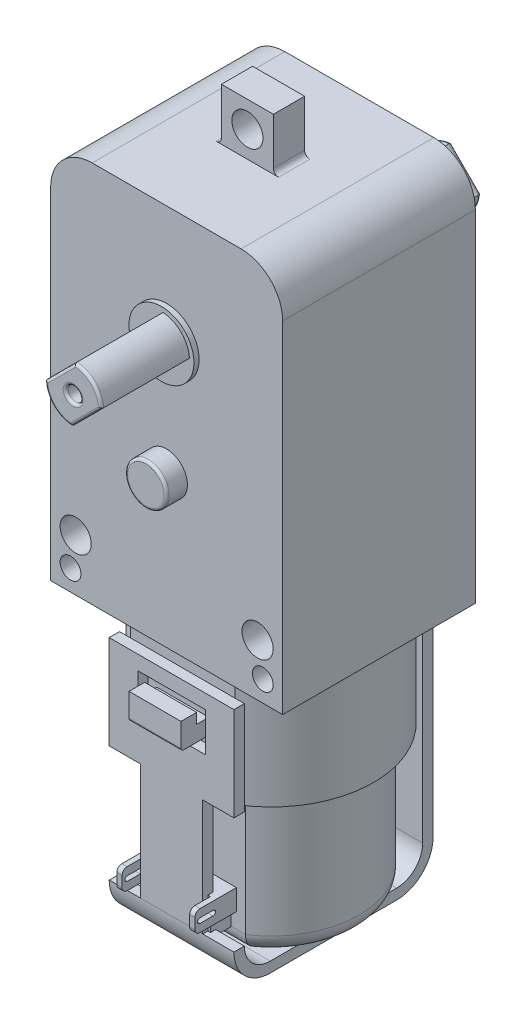
SolidWorks part; units mm, degrees
ref_plane "Front Plane" through (0, 0, 0) normal (0, 0, 1) x (1, 0, 0)
ref_plane "Top Plane" through (0, 0, 0) normal (0, 1, 0) x (1, 0, 0)
ref_plane "Right Plane" through (0, 0, 0) normal (1, 0, 0) x (0, 0, -1)
sketch "Sketch1" plane through (0, 0, 0) normal (0, 0, 1) x (1, 0, 0)
  line L0 (0, 24.4324) -> (0, -59.3504) construction
  line L1 (-11.16, -18.4) -> (11.16, -18.4)
  line L2 (-11.16, -18.4) -> (-11.16, 14.4)
  line L3 (-7.16, 18.4) -> (7.16, 18.4)
  line L4 (11.16, -18.4) -> (11.16, 14.4)
  line L5 (-11.16, -18.4) -> (11.16, 18.4) construction
  line L6 (-11.16, 18.4) -> (11.16, -18.4) construction
  line L7 (8.75, 21.9889) -> (8.75, -24.3513) construction
  line L8 (4.4968, -13.4) -> (12.7809, -13.4) construction
  arc A0 (7.16, 18.4) -> (11.16, 14.4) centre (7.16, 14.4) cw
  arc A1 (-11.16, 14.4) -> (-7.16, 18.4) centre (-7.16, 14.4) cw
  circle A2 centre (8.75, -13.4) radius 1.5
  circle A4 centre (-8.75, -13.4) radius 1.5
  point P0 (0, 0)
  dimension "D3" = 4
  dimension "D7" = 3
  dimension "D1" = 22.32
  dimension "D2" = 36.8
  dimension "D4" = 8.75
  dimension "D5" = 5
extrude "Boss-Extrude1" add sketch "Sketch1" along normal mid plane 18.54
sketch "Sketch2" plane through (0, 0, 9.27) normal (0, 0, 1) x (1, 0, 0)
  line L0 (0, 22.2467) -> (0, -30.3697) construction
  line L1 (10.25, -9.3804) -> (10.25, -17.9489) construction
  line L2 (12.457, -16.4) -> (4.3496, -16.4) construction
  line L3 (-11.16, -18.4) -> (11.16, -18.4) construction
  circle A0 centre (8.75, -13.4) radius 1.5 construction
  circle A1 centre (9.25, -16.4) radius 1
  circle A2 centre (-9.25, -16.4) radius 1
  dimension "D1" = 2
  dimension "D2" = 2
extrude "Cut-Extrude1" cut sketch "Sketch2" against normal blind 4.5
mirror "Mirror1" about plane through (0, 0, 0) normal (0, 0, 1) of "Cut-Extrude1"
sketch "Sketch3" plane through (0, 0, 0) normal (0, 0, 1) x (1, 0, 0)
  line L0 (0, 26.7509) -> (0, -20.1795) construction
  line L1 (7.16, 18.4) -> (-7.16, 18.4) construction
  line L2 (-2.5, 18.4) -> (2.5, 18.4)
  line L3 (-2.5, 18.4) -> (-2.5, 23.4)
  line L4 (-2.5, 23.4) -> (2.5, 23.4)
  line L5 (2.5, 18.4) -> (2.5, 23.4)
  line L6 (-2.5, 18.4) -> (2.5, 23.4) construction
  line L7 (-2.5, 23.4) -> (2.5, 18.4) construction
  line L8 (-13.5279, -13.4) -> (13.2542, -13.4) construction
  circle A0 centre (0, 20.9) radius 1.5
  point P3 (0, 20.9)
  dimension "D3" = 3
  dimension "D1" = 5
  dimension "D2" = 5
extrude "Boss-Extrude2" add sketch "Sketch3" along normal mid plane 3
fillet "Fillet1" radius 0.5 2 edges at (-2.5, 18.4, 0) (2.5, 18.4, 0)
sketch "Sketch4" plane through (0, -18.4, 0) normal (0, -1, 0) x (1, 0, 0)
  line L0 (0, 12.3097) -> (0, -10.2788) construction
  line L1 (-13.8041, 0) -> (13.9573, 0) construction
  line L2 (-11.16, -9.27) -> (11.16, -9.27) construction
  line L3 (-5.0289, -9.27) -> (5.0289, -9.27)
  line L4 (6.1994, -0.7811) -> (-4.4564, -0.7811) construction
  line L5 (-5.0289, 7.7077) -> (5.0289, 7.7077)
  line L6 (5.0289, 11.6793) -> (5.0289, -13.5417) construction
  line L7 (7.16, -9.27) -> (-7.16, -9.27) construction
  arc A0 (-5.0289, 7.7077) -> (-5.0289, -9.27) centre (0, -0.7811) ccw
  arc A1 (5.0289, -9.27) -> (5.0289, 7.7077) centre (0, -0.7811) ccw
  dimension "D1" = 0.7811
  dimension "D3" = 10.0579
extrude "Boss-Extrude3" add sketch "Sketch4" along normal blind 11.33
sketch "Sketch5" plane through (0, -29.73, 0) normal (0, -1, 0) x (1, 0, 0)
  line L4 (4.6295, 6.3077) -> (-4.6295, 6.3077)
  line L5 (-4.6295, -7.87) -> (4.6295, -7.87)
  line L6 (4.6295, 6.3077) -> (-4.6295, 6.3077)
  line L7 (-4.6295, -7.87) -> (4.6295, -7.87)
  arc A5 (4.6295, -7.87) -> (4.6295, 6.3077) centre (0, -0.7811) ccw
  arc A6 (-4.6295, 6.3077) -> (-4.6295, -7.87) centre (0, -0.7811) ccw
  arc A7 (4.6295, -7.87) -> (4.6295, 6.3077) centre (0, -0.7811) ccw
  arc A8 (-4.6295, 6.3077) -> (-4.6295, -7.87) centre (0, -0.7811) ccw
  dimension "D1" = 1.4
extrude "Boss-Extrude4" add sketch "Sketch5" along normal blind 8
sketch "Sketch6" plane through (0, -37.73, 0) normal (0, -1, 0) x (1, 0, 0)
  line L2 (4.6295, 6.3077) -> (-4.6295, 6.3077)
  line L3 (-4.6295, -7.87) -> (4.6295, -7.87)
  line L4 (4.6295, 6.3077) -> (-4.6295, 6.3077)
  line L5 (-4.6295, -7.87) -> (4.6295, -7.87)
  arc A2 (4.6295, -7.87) -> (4.6295, 6.3077) centre (0, -0.7811) ccw
  arc A3 (-4.6295, 6.3077) -> (-4.6295, -7.87) centre (0, -0.7811) ccw
  arc A4 (4.6295, -7.87) -> (4.6295, 6.3077) centre (0, -0.7811) ccw
  arc A5 (-4.6295, 6.3077) -> (-4.6295, -7.87) centre (0, -0.7811) ccw
  dimension "D1" = 0
sketch "Sketch8" plane through (0, -37.73, 0) normal (0, -1, 0) x (1, 0, 0)
  line L2 (4.6295, 6.3077) -> (-4.6295, 6.3077)
  line L3 (-4.6295, -7.87) -> (4.6295, -7.87)
  line L4 (4.6295, 6.3077) -> (-4.6295, 6.3077)
  line L5 (-4.6295, -7.87) -> (4.6295, -7.87)
  arc A2 (4.6295, -7.87) -> (4.6295, 6.3077) centre (0, -0.7811) ccw
  arc A3 (-4.6295, 6.3077) -> (-4.6295, -7.87) centre (0, -0.7811) ccw
  arc A4 (4.6295, -7.87) -> (4.6295, 6.3077) centre (0, -0.7811) ccw
  arc A5 (-4.6295, 6.3077) -> (-4.6295, -7.87) centre (0, -0.7811) ccw
  dimension "D1" = 0
extrude "Boss-Extrude7" add sketch "Sketch8" along normal blind 5.5 separate body
fillet "Fillet2" radius 1.75 4 edges at (0, -43.23, -7.87) (-8.4667, -43.23, -0.7811) (0, -43.23, 6.3077) (8.4667, -43.23, -0.7811)
ref_plane "Plane1" through (0, 0, -0.7811) normal (0, 0, 1) x (1, 0, 0)
sketch "Sketch9" plane through (0, 0, 0) normal (1, 0, 0) x (0, 0, -1)
  line L0 (0, 26.0448) -> (0, -5.819) construction
  line L1 (-16.1844, 0) -> (23.9105, 0) construction
  line L2 (0.3625, -46.2168) -> (0.3625, -15.0095) construction
  line L3 (-11.2862, -24.065) -> (28.4552, -24.065) construction
  line L4 (9.27, -29.73) -> (9.27, -18.4) construction
  line L5 (-7.7077, -29.73) -> (-7.7077, -18.4) construction
  line L6 (10.45, -22.735) -> (11.95, -22.735)
  line L7 (9.27, -23.735) -> (9.27, -25.235)
  line L8 (9.27, -25.235) -> (11.7, -25.235)
  line L9 (11.95, -22.735) -> (11.95, -24.985)
  line L13 (9.27, -23.735) -> (10.45, -23.735)
  line L14 (10.45, -22.735) -> (10.45, -23.735)
  arc A0 (11.7, -25.235) -> (11.95, -24.985) centre (11.7, -24.985) ccw
  point P12 (-7.7077, -24.065)
  point P21 (9.86, -23.735)
  point P23 (11.95, -25.235)
  dimension "D6" = 0.25
  dimension "D1" = 2.68
  dimension "D2" = 2.5
  dimension "D3" = 1.17
  dimension "D4" = 1.5
  dimension "D5" = 1.5
  dimension "D7" = 0.3625
extrude "Boss-Extrude8" add sketch "Sketch9" along normal mid plane 5
sketch "Sketch10" plane through (0, -43.23, 0) normal (0, -1, 0) x (1, 0, 0)
  line L0 (0, 11.1876) -> (0, -13.2249) construction
  line L1 (-12.2393, -0.7811) -> (13.3607, -0.7811) construction
  line L2 (-8.6431, 2.2189) -> (11.2966, 2.2189) construction
  line L3 (-3.9624, 2.2189) -> (3.9624, 2.2189)
  arc A0 (-3.9624, 2.2189) -> (3.9624, 2.2189) centre (0, -0.7811) ccw
  dimension "D1" = 9.94
  dimension "D2" = 3
extrude "Boss-Extrude10" add sketch "Sketch10" along normal blind 2
sketch "Sketch11" plane through (0, -45.23, 0) normal (0, -1, 0) x (1, 0, 0)
  line L0 (-11.9473, -0.8405) -> (14.0438, -0.8405) construction
  line L1 (0, 11.5108) -> (0, -13.1917) construction
  circle A0 centre (0, -0.8405) radius 0.99
  dimension "D1" = 1.98
  dimension "D2" = 0.8405
extrude "Boss-Extrude11" add sketch "Sketch11" along normal blind 0.75
mirror "Mirror2" about plane through (0, 0, -0.7811) normal (0, 0, 1) of "Boss-Extrude8"
fillet "Fillet3" radius 0.2 1 edges at (0, -45.98, -1.8305)
fillet "Fillet4" radius 0.5 6 edges at (0, -45.23, -5.7511) (0, -43.23, 2.2189) (-3.9624, -44.23, 2.2189) (3.9624, -44.23, 2.2189) (0, -43.23, -5.7511) (0, -45.23, 2.2189)
ref_plane "Plane2" through (0, -39, 0) normal (0, 1, 0) x (1, 0, 0)
sketch "Sketch16" plane through (0, 0, 0) normal (1, 0, 0) x (0, 0, -1)
  line L0 (-23.8246, 0) -> (20.0239, 0) construction
  line L1 (0, 7.883) -> (0, -51.0021) construction
  line L2 (10.45, -23.735) -> (9.27, -23.735) construction
  line L3 (-8.8877, -23.735) -> (-7.7077, -23.735) construction
  line L4 (-8.2977, -20.8005) -> (-8.2977, -41)
  line L5 (-5.2977, -44) -> (6.86, -44)
  line L6 (9.86, -21) -> (9.86, -41)
  arc A0 (6.86, -44) -> (9.86, -41) centre (6.86, -41) ccw
  arc A1 (-8.2977, -41) -> (-5.2977, -44) centre (-5.2977, -41) ccw
  point P10 (9.86, -23.735)
  point P15 (-8.2977, -23.735)
  dimension "D1" = 3
  dimension "D2" = 20
  dimension "D3" = 44
  dimension "D4" = 20.8005
extrude "Extrude-Thin2" add sketch "Sketch16" along normal mid plane 12 thin thin type mid plane wall 1
sketch "Sketch17" plane through (0, -44.5, 0) normal (0, -1, 0) x (1, 0, 0)
  circle A0 centre (0, -0.7811) radius 5.4444
  dimension "D1" = 10.8888
extrude "Cut-Extrude4" cut sketch "Sketch17" against normal up to surface (1 mm away) up to face at (0, -43.5, -0.7811)
sketch "Sketch18" plane through (0, 0, 8.7977) normal (0, 0, 1) x (1, 0, 0)
  line L0 (-6, -41) -> (-6, -20.8005) construction
  line L1 (0, -48.1306) -> (0, -15.5328) construction
  line L2 (-27.9579, 0) -> (28.0521, 0) construction
  line L3 (6, -41) -> (3, -41)
  line L4 (3, -29.8239) -> (3, -41)
  line L5 (-3.25, -22.1832) -> (3.25, -22.1832)
  line L6 (-3.25, -22.1832) -> (-3.25, -25.9332)
  line L7 (-3.25, -25.9332) -> (3.25, -25.9332)
  line L8 (3.25, -22.1832) -> (3.25, -25.9332)
  line L9 (-6, -29.8239) -> (-3, -29.8239)
  line L10 (-6, -29.8239) -> (-6, -41)
  line L11 (-6, -41) -> (-3, -41)
  line L12 (-3, -29.8239) -> (-3, -41)
  line L13 (6, -41) -> (-6, -41) construction
  line L14 (6, -29.8239) -> (6, -41)
  line L15 (6, -29.8239) -> (3, -29.8239)
  point P2 (0, -25.9332)
  dimension "D1" = 3.75
  dimension "D2" = 6.5
  dimension "D3" = 22.1832
  dimension "D4" = 29.8239
  dimension "D5" = 3
extrude "Cut-Extrude6" cut sketch "Sketch18" against normal up to surface (1 mm away) up to face at (0, -24.485, 7.7977)
sketch "Sketch14" plane through (0, -39, 0) normal (0, 1, 0) x (1, 0, 0)
  line L0 (0, 15.2148) -> (0, -12.3775) construction
  line L1 (4.6295, -6.3077) -> (-4.6295, -6.3077) construction
  line L2 (-3.25, -8.3077) -> (3.25, -8.3077)
  line L3 (-3.25, -8.3077) -> (-3.25, -6.3077)
  line L4 (-3.25, -6.3077) -> (3.25, -6.3077)
  line L5 (3.25, -8.3077) -> (3.25, -6.3077)
  line L6 (-3.25, -8.3077) -> (3.25, -6.3077) construction
  line L7 (-3.25, -6.3077) -> (3.25, -8.3077) construction
  point P2 (0, -7.3077)
  dimension "D1" = 6.5
  dimension "D2" = 2
extrude "Boss-Extrude13" add sketch "Sketch14" against normal blind 2.5 and the other way blind 1
sketch "Sketch15" plane through (-3.25, 0, 0) normal (-1, 0, 0) x (0, 0, 1)
  line L0 (6.3077, -38) -> (6.3077, -41.48) construction
  line L1 (6.3077, -38) -> (9.8077, -38)
  line L2 (6.3077, -38) -> (6.3077, -40)
  line L3 (6.3077, -40) -> (9.8077, -40)
  line L4 (10.3077, -38.5) -> (10.3077, -39.5)
  line L5 (6.3077, -38) -> (8.3077, -38) construction
  line L6 (9.8077, -39) -> (8.5577, -39) construction
  line L7 (12.2265, -39) -> (-12.2265, -39) construction
  line L8 (9.8077, -39.2334) -> (8.5577, -39.2334)
  line L9 (9.8077, -38.7666) -> (8.5577, -38.7666)
  arc A0 (9.8077, -40) -> (10.3077, -39.5) centre (9.8077, -39.5) ccw
  arc A1 (9.8077, -38) -> (10.3077, -38.5) centre (9.8077, -38.5) cw
  arc A2 (9.8077, -39.2334) -> (9.8077, -38.7666) centre (9.8077, -39) ccw
  arc A3 (8.5577, -38.7666) -> (8.5577, -39.2334) centre (8.5577, -39) ccw
  point P10 (10.3077, -40)
  point P13 (10.3077, -38)
  point P18 (9.1827, -39)
  dimension "D3" = 0.5
  dimension "D4" = 0.2334
  dimension "D5" = 1.25
  dimension "D1" = 4
  dimension "D2" = 2
extrude "Boss-Extrude14" add sketch "Sketch15" along normal blind 0.5
mirror "Mirror3" about plane through (0, 0, 0) normal (1, 0, 0) of "Boss-Extrude14"
extrude "Boss-Extrude17" add sketch "Sketch6" along normal blind 2
sketch "Sketch21" plane through (0, 0, 7.7977) normal (0, 0, 1) x (1, 0, 0)
  line L4 (2.5, -23.735) -> (-2.5, -23.735)
  line L5 (-2.5, -23.735) -> (-2.5, -25.235)
  line L6 (-2.5, -25.235) -> (2.5, -25.235)
  line L7 (2.5, -25.235) -> (2.5, -23.735)
  line L8 (2.5, -23.735) -> (-2.5, -23.735)
  line L9 (-2.5, -23.735) -> (-2.5, -25.235)
  line L10 (-2.5, -25.235) -> (2.5, -25.235)
  line L11 (2.5, -25.235) -> (2.5, -23.735)
  dimension "D1" = 0
extrude "Boss-Extrude18" add sketch "Sketch21" along normal up to next
sketch "Sketch22" plane through (0, 0, 9.27) normal (0, 0, 1) x (1, 0, 0)
  line L0 (-17.9469, 7.15) -> (22.414, 7.15) construction
  line L1 (0, 27.5294) -> (0, -52.0362) construction
  line L2 (7.16, 18.4) -> (-7.16, 18.4) construction
  circle A0 centre (0, 7.15) radius 2.7
  circle A1 centre (0, 7.15) radius 0.7
  dimension "D2" = 5.4
  dimension "D3" = 2
  dimension "D1" = 11.25
extrude "Boss-Extrude19" add sketch "Sketch22" along normal blind 9
mirror "Mirror4" about plane through (0, 0, 0) normal (0, 0, 1) of "Boss-Extrude19"
sketch "Sketch23" plane through (0, 0, 18.27) normal (0, 0, 1) x (1, 0, 0)
  line L0 (0, 27.0039) -> (0, -48.4626) construction
  line L2 (-16.42, 0) -> (16.5519, 0) construction
  line L3 (0, 7.15) -> (-4.7321, 2.4179) construction
  line L4 (-2.6958, 6.9998) -> (0.1502, 9.8458)
  line L5 (-0.1502, 4.4542) -> (2.6958, 7.3002)
  arc A0 (0.1502, 9.8458) -> (-2.6958, 6.9998) centre (0, 7.15) ccw
  circle A1 centre (0, 7.15) radius 2.7
  arc A2 (-0.1502, 4.4542) -> (2.6958, 7.3002) centre (0, 7.15) ccw
  dimension "D1" = 45
  dimension "D3" = 3.6
  dimension "D4" = 1.8
  dimension "D2" = 0
extrude "Cut-Extrude7" cut sketch "Sketch23" against normal blind 9
sketch "Sketch24" plane through (0, 0, 9.27) normal (0, 0, 1) x (1, 0, 0)
  circle A0 centre (0, 7.15) radius 0.7 construction
  circle A1 centre (0, 7.15) radius 0.7
  circle A2 centre (0, 7.15) radius 3.125
  dimension "D1" = 6.25
extrude "Boss-Extrude20" add sketch "Sketch24" along normal blind 0.5
mirror "Mirror5" about plane through (0, 0, 0) normal (0, 0, 1) of "Boss-Extrude20"
sketch "Sketch25" plane through (0, 0, -18.27) normal (0, 0, -1) x (-1, 0, 0)
  line L0 (4.9981, 12.1481) -> (-5.1404, 2.0096) construction
  line L1 (-2.6958, 6.9998) -> (0.1502, 9.8458)
  line L2 (-0.1502, 4.4542) -> (2.6958, 7.3002)
  line L3 (0, 13.72) -> (0, -2.7867) construction
  circle A0 centre (0, 7.15) radius 0.7 construction
  circle A1 centre (0, 7.15) radius 0.7 construction
  circle A2 centre (0, 7.15) radius 2.7 construction
  arc A3 (0.1502, 9.8458) -> (-2.6958, 6.9998) centre (0, 7.15) ccw
  arc A4 (-0.1502, 4.4542) -> (2.6958, 7.3002) centre (0, 7.15) ccw
  dimension "D1" = 45
  dimension "D2" = 3.6
  dimension "D3" = 1.8
extrude "Cut-Extrude8" cut sketch "Sketch25" against normal blind 8.5
sketch "Sketch26" plane through (0, 0, 9.27) normal (0, 0, 1) x (1, 0, 0)
  line L0 (0, 25.8818) -> (0, -10.4032) construction
  line L1 (-16.5711, -3.85) -> (19.1509, -3.85) construction
  line L2 (-14.3189, 7.15) -> (17.2115, 7.15) construction
  circle A0 centre (0, 7.15) radius 0.7 construction
  circle A1 centre (0, 7.15) radius 0.7 construction
  circle A2 centre (0, -3.85) radius 2
  dimension "D2" = 4
  dimension "D1" = 11
extrude "Boss-Extrude21" add sketch "Sketch26" along normal blind 2
fillet "Fillet5" radius 0.25 11 edges at (0.7, 7.15, -18.27) (-1.9092, 9.0592, -18.27) (-1.2728, 5.8772, -18.27) (1.9092, 5.2408, -18.27) (1.2728, 8.4228, -18.27) (0.7, 7.15, 18.27) (-1.9092, 5.2408, 18.27) (-1.2728, 8.4228, 18.27) (1.9092, 9.0592, 18.27) (1.2728, 5.8772, 18.27) (2, -3.85, 11.27)
equation "\".5mmm\"=9"
